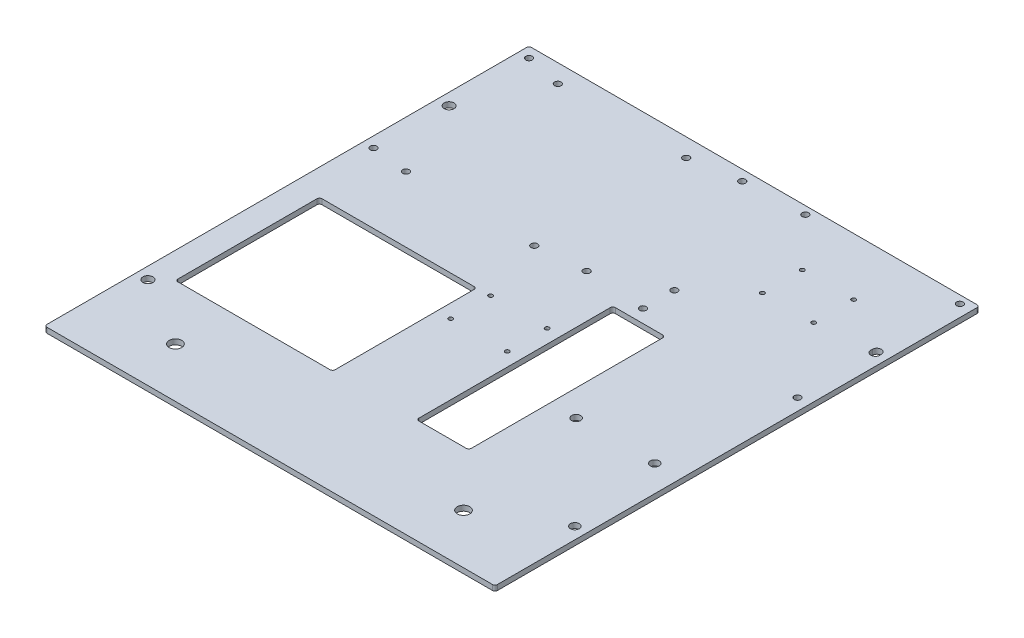
SolidWorks part; units mm, degrees
material "3.3535 (EN-AW 5154A)"
ref_plane "Ebene vorne" through (0, 0, 0) normal (0, 0, 1) x (1, 0, 0)
ref_plane "Ebene oben" through (0, 0, 0) normal (0, 1, 0) x (1, 0, 0)
ref_plane "Ebene rechts" through (0, 0, 0) normal (1, 0, 0) x (0, 0, -1)
sketch "Skizze1" plane through (0, 0, 0) normal (0, 1, 0) x (1, 0, 0)
  line L0 (-86, -92.5) -> (86, 92.5) construction
  line L1 (-86, 92.5) -> (86, 92.5)
  line L2 (-86, 92.5) -> (-86, -92.5)
  line L3 (-86, -92.5) -> (86, -92.5)
  line L4 (86, 92.5) -> (86, -92.5)
  point P4 (0, 0)
  dimension "D1" = 172
  dimension "D2" = 185
extrude "Aufsatz-Linear austragen1" add sketch "Skizze1" along normal blind 2
hole_wizard "Durchgangsloch für M31" positions "Skizze4" profile "Skizze3" hole size "M3" standard "ANSI Metrisch" end condition through all
sketch "Skizze4" plane through (0, 2, 0) normal (0, 1, 0) x (1, 0, 0)
  line L1 (-81.5, 57.5) -> (81.5, 57.5)
  line L2 (-81.5, 57.5) -> (-81.5, -57.5)
  line L3 (-81.5, -57.5) -> (81.5, -57.5)
  line L4 (81.5, 57.5) -> (81.5, -57.5)
  line L5 (86, 92.5) -> (-86, 92.5) construction
  line L6 (-86, -92.5) -> (86, -92.5) construction
  line L7 (-86, 92.5) -> (-86, -92.5) construction
  line L8 (86, -92.5) -> (86, 92.5) construction
  point P6 (81.5, -57.5)
  dimension "D1" = 35
  dimension "D2" = 35
  dimension "D3" = 4.5
  dimension "D4" = 4.5
sketch "Skizze3" plane through (81.5, 2, 57.5) normal (1, 0, 0) x (0, 0, 1)
  line L0 (0, 0) -> (0, 2)
  line L1 (0, 2) -> (1.7, 2)
  line L2 (1.7, 2) -> (1.7, 0)
  line L5 (1.7, 0) -> (0, 0)
  line L11 (0, -6.35) -> (0, 107.95) construction
  dimension "Bohrerdurchmesser" = 3.4
  dimension "Bohrungstiefe" = 2
hole_wizard "Ø3.8 (3.8) Durchmesser Bohrung1" positions "Skizze17" profile "Skizze18" hole size "Ø3.8" standard "ANSI Metrisch"
sketch "Skizze17" plane through (0, 2, 0) normal (0, 1, 0) x (1, 0, 0)
  point P0 (-81.5, -57.5)
  point P3 (-81.5, 57.5)
sketch "Skizze18" plane through (-81.5, 2, 57.5) normal (1, 0, 0) x (0, 0, 1)
  line L0 (0, 0) -> (0, 11.1416)
  line L1 (0, 11.1416) -> (1.9, 10)
  line L2 (1.9, 10) -> (1.9, 0)
  line L5 (1.9, 0) -> (0, 0)
  line L10 (0, 11.1416) -> (-1.9, 10) construction
  line L11 (0, -6.35) -> (0, 107.95) construction
  dimension "Bohrerdurchmesser" = 3.8
  dimension "Bohrungstiefe" = 10
  dimension "Spitzenwinkel" = 118
hole_wizard "Ø3.4 (3.4) Durchmesser Langloch1" positions "Skizze19" profile "Skizze21" size "Ø3.4" standard "ANSI Metrisch" slot yes end condition through all
sketch "Skizze19" plane through (0, 2, 0) normal (0, 1, 0) x (1, 0, 0)
  line L0 (81.5, 59.5) -> (81.5, 55.5) construction
  line L1 (81.5, 57.5) -> (81.5, -57.5) construction
  point P0 (81.5, 57.5)
  dimension "D1" = 4
sketch "Skizze21" plane through (81.5, 2, -57.5) normal (1, 0, 0) x (0, 0, 1)
  line L0 (0, 0) -> (0, 2)
  line L1 (0, 2) -> (1.7, 2)
  line L2 (1.7, 2) -> (1.7, 0)
  line L5 (1.7, 0) -> (0, 0)
  line L11 (0, -6.35) -> (0, 107.95) construction
  dimension "Bohrerdurchmesser" = 3.4
  dimension "Bohrungstiefe" = 2
sketch "Skizze5" plane through (0, 0, 0) normal (0, 1, 0) x (1, 0, 0)
  line L0 (-86, 92.5) -> (-86, -92.5) construction
  line L1 (16, 22.5) -> (36, 22.5)
  line L4 (36, 22.5) -> (36, -52.5)
  line L5 (-76, -52.5) -> (-16, -52.5)
  line L6 (-76, -52.5) -> (-76, 2.5)
  line L7 (-76, 2.5) -> (-16, 2.5)
  line L8 (-16, -52.5) -> (-16, 2.5)
  line L10 (86, 92.5) -> (-86, 92.5) construction
  line L11 (-86, -92.5) -> (86, -92.5) construction
  line L12 (16, 22.5) -> (16, -52.5)
  line L13 (16, -52.5) -> (36, -52.5)
  line L14 (86, -92.5) -> (86, 92.5) construction
  dimension "D1" = 50
  dimension "D2" = 20
  dimension "D3" = 10
  dimension "D5" = 70
  dimension "D6" = 90
  dimension "D7" = 40
  dimension "D8" = 60
extrude "Schnitt-Linear austragen1" cut sketch "Skizze5" along normal blind 10
hole_wizard "Ø4.3 (4.79) Durchmesser Bohrung1" positions "Skizze6" profile "Skizze7" hole size "Ø4.3" standard "ANSI Metrisch" end condition through all
sketch "Skizze6" plane through (0, 2, 0) normal (0, 1, 0) x (1, 0, 0)
  line L3 (-55, -73.5) -> (55, -73.5) construction
  point P0 (-55, -73.5)
  point P2 (55, -73.5)
  point P18 (0, -73.5)
  dimension "D1" = 73.5
  dimension "D2" = 110
sketch "Skizze7" plane through (-55, 2, 73.5) normal (1, 0, 0) x (0, 0, 1)
  line L0 (0, 0) -> (0, 2)
  line L1 (0, 2) -> (2.395, 2)
  line L2 (2.395, 2) -> (2.395, 0)
  line L5 (2.395, 0) -> (0, 0)
  line L11 (0, -6.35) -> (0, 107.95) construction
  dimension "Bohrerdurchmesser" = 4.79
  dimension "Bohrungstiefe" = 2
hole_wizard "Durchgangsloch für M32" positions "Skizze8" profile "Skizze9" hole size "M3" standard "ANSI Metrisch" end condition through all
sketch "Skizze8" plane through (0, 2, 0) normal (0, 1, 0) x (1, 0, 0)
  line L0 (46, -21.5) -> (76, -21.5)
  line L5 (-86, -92.5) -> (86, -92.5) construction
  line L6 (86, -92.5) -> (86, 92.5) construction
  point P0 (46, -21.5)
  point P2 (76, -21.5)
  dimension "D1" = 71
  dimension "D2" = 30
  dimension "D3" = 10
sketch "Skizze9" plane through (46, 2, 21.5) normal (1, 0, 0) x (0, 0, 1)
  line L0 (0, 0) -> (0, 2)
  line L1 (0, 2) -> (1.7, 2)
  line L2 (1.7, 2) -> (1.7, 0)
  line L5 (1.7, 0) -> (0, 0)
  line L11 (0, -6.35) -> (0, 107.95) construction
  dimension "Bohrerdurchmesser" = 3.4
  dimension "Bohrungstiefe" = 2
hole_wizard "M3x0.5 Gewindebohrung2" positions "Skizze10" profile "Skizze11" tap size "M3x0.5" standard "ANSI Metric" end condition through all
sketch "Skizze10" plane through (0, 2, 0) normal (0, 1, 0) x (1, 0, 0)
  line L1 (-68, 27.5) -> (-19, 27.5)
  line L2 (-68, 27.5) -> (-68, 85.5)
  line L3 (-68, 85.5) -> (-19, 85.5)
  line L4 (-19, 27.5) -> (-19, 85.5)
  line L5 (-86, 92.5) -> (-86, -92.5) construction
  line L6 (86, 92.5) -> (-86, 92.5) construction
  line L8 (-0.6, 29.1) -> (-82, 29.1)
  line L9 (-0.6, 29.1) -> (-0.6, 88.5)
  line L10 (-0.6, 88.5) -> (-82, 88.5)
  line L11 (-82, 29.1) -> (-82, 88.5)
  point P1 (-68, 27.5)
  point P2 (-19, 85.5)
  point P45 (-68, 85.5)
  point P46 (-19, 27.5)
  point P61 (-0.6, 29.1)
  point P62 (-82, 88.5)
  point P305 (-0.6, 88.5)
  point P306 (-82, 29.1)
  dimension "D1" = 58
  dimension "D2" = 49
  dimension "D3" = 18
  dimension "D4" = 7
  dimension "D5" = 4
  dimension "D6" = 4
  dimension "D7" = 59.4
  dimension "D8" = 81.4
sketch "Skizze11" plane through (-68, 2, -27.5) normal (1, 0, 0) x (0, 0, 1)
  line L0 (0, 0) -> (0, 2)
  line L1 (0, 2) -> (1.25, 2)
  line L2 (1.25, 2) -> (1.25, 0)
  line L5 (1.25, 0) -> (0, 0)
  line L11 (0, -6.35) -> (0, 107.95) construction
  dimension "Bohrerdurchmesser" = 2.5
  dimension "Bohrungstiefe" = 2
hole_wizard "M3x0.5 Gewindebohrung3" positions "Skizze12" profile "Skizze13" tap size "M3x0.5" standard "ANSI Metrisch" end condition through all
sketch "Skizze12" plane through (0, 2, 0) normal (0, 1, 0) x (1, 0, 0)
  line L1 (22.5, 27.5) -> (81.5, 27.5)
  line L2 (22.5, 27.5) -> (22.5, 89.5)
  line L3 (22.5, 89.5) -> (81.5, 89.5)
  line L4 (81.5, 27.5) -> (81.5, 89.5)
  line L5 (86, -92.5) -> (86, 92.5) construction
  line L6 (86, 92.5) -> (-86, 92.5) construction
  point P1 (22.5, 27.5)
  point P2 (81.5, 89.5)
  point P51 (22.5, 89.5)
  point P52 (81.5, 27.5)
  point P58 (22.5, 39.5)
  dimension "D1" = 62
  dimension "D2" = 59
  dimension "D3" = 4.5
  dimension "D4" = 3
  dimension "D5" = 12
sketch "Skizze13" plane through (22.5, 2, -27.5) normal (1, 0, 0) x (0, 0, 1)
  line L0 (0, 0) -> (0, 2)
  line L1 (0, 2) -> (1.25, 2)
  line L2 (1.25, 2) -> (1.25, 0)
  line L5 (1.25, 0) -> (0, 0)
  line L11 (0, -6.35) -> (0, 107.95) construction
  dimension "Nenndurchmesser (Haupt)" = 2.5
  dimension "Bohrungstiefe" = 2
fillet "Verrundung1" radius 1 12 edges at (36, 1, -22.5) (-16, 1, -2.5) (-16, 1, 52.5) (-76, 1, 52.5) (-76, 1, -2.5) (-86, 1, -92.5) (86, 1, -92.5) (-86, 1, 92.5) (86, 1, 92.5) (36, 1, 52.5) (16, 1, 52.5) (16, 1, -22.5)
sketch "Skizze14" plane through (0, 2, 0) normal (0, 1, 0) x (1, 0, 0)
  line L0 (-85, -92.5) -> (85, -92.5) construction
  line L1 (10.795, -12.62) -> (-10.795, -12.62)
  line L2 (10.795, -12.62) -> (10.795, 2.62)
  line L3 (10.795, 2.62) -> (-10.795, 2.62)
  line L4 (-10.795, -12.62) -> (-10.795, 2.62)
  point P4 (10.795, -5)
  point P7 (0, -12.62)
  point P8 (0, -92.5)
  dimension "D1" = 87.5
  dimension "D2" = 21.59
  dimension "D3" = 15.24
hole_wizard "M2x0.4 Gewindebohrung1" positions "Skizze15" profile "Skizze16" tap size "M2x0.4" standard "ANSI Metrisch" end condition through all
sketch "Skizze15" plane through (0, 2, 0) normal (0, 1, 0) x (1, 0, 0)
  line L1 (40.205, 55.38) -> (59.795, 55.38)
  line L2 (40.205, 55.38) -> (40.205, 70.62)
  line L3 (40.205, 70.62) -> (59.795, 70.62)
  line L4 (59.795, 55.38) -> (59.795, 70.62)
  point P0 (10.795, -12.62)
  point P3 (-10.795, -12.62)
  point P6 (-10.795, 2.62)
  point P9 (10.795, 2.62)
  point P42 (50, 55.38)
  point P43 (40.205, 63)
  point P46 (40.205, 70.62)
  point P49 (40.205, 55.38)
  point P52 (59.795, 55.38)
  point P55 (59.795, 70.62)
  dimension "D1" = 15.24
  dimension "D2" = 19.59
  dimension "D3" = 50
  dimension "D4" = 63
sketch "Skizze16" plane through (10.795, 2, 12.62) normal (1, 0, 0) x (0, 0, 1)
  line L0 (0, 0) -> (0, 2)
  line L1 (0, 2) -> (0.8, 2)
  line L2 (0.8, 2) -> (0.8, 0)
  line L5 (0.8, 0) -> (0, 0)
  line L11 (0, -6.35) -> (0, 107.95) construction
  dimension "Nenndurchmesser (Haupt)" = 1.6
  dimension "Bohrungstiefe" = 2
